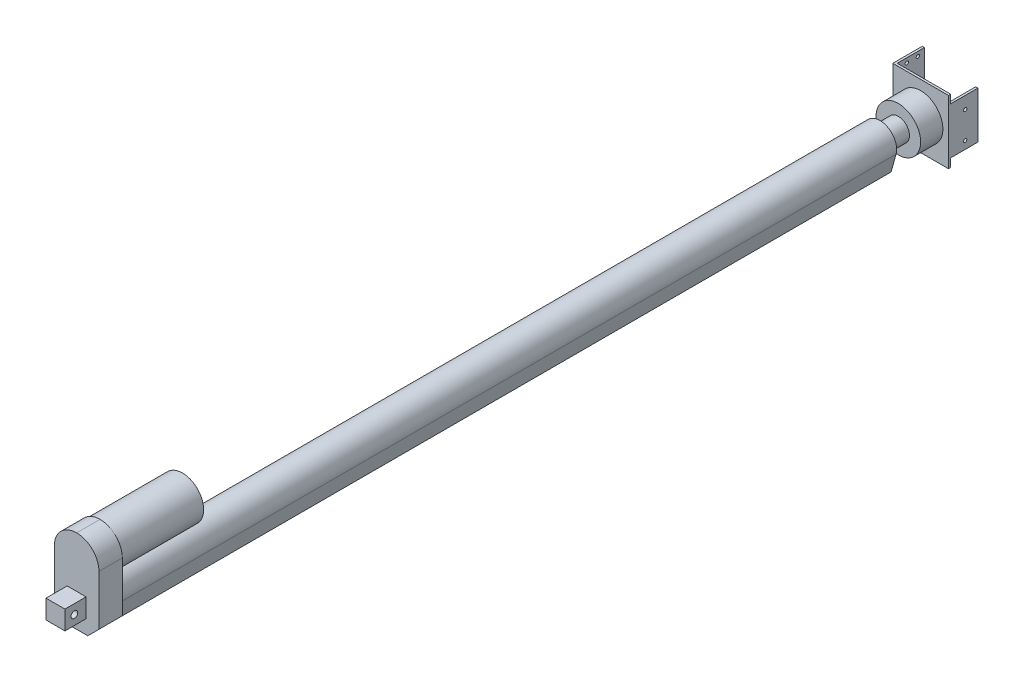
SolidWorks part; units mm, degrees
ref_plane "前视基准面" through (0, 0, 0) normal (0, 0, 1) x (1, 0, 0)
ref_plane "上视基准面" through (0, 0, 0) normal (0, 1, 0) x (1, 0, 0)
ref_plane "右视基准面" through (0, 0, 0) normal (1, 0, 0) x (0, 0, -1)
other "Configuration Table"
sketch "草图1" plane through (0, 0, 0) normal (0, 0, 1) x (1, 0, 0)
  line L1 (-20, 37.5) -> (20, 37.5)
  line L2 (-20, 37.5) -> (-20, -37.5)
  line L3 (-20, -37.5) -> (20, -37.5)
  line L4 (20, 37.5) -> (20, -37.5)
  dimension "D1" = 75
  dimension "D2" = 40
  dimension "D3" = 20
  dimension "D4" = 37.5
extrude "凸台-拉伸1" add sketch "草图1" along normal blind 21
fillet "圆角1" radius 20 2 edges at (-20, 37.5, 10.5) (20, 37.5, 10.5)
chamfer "倒角1" distance 10 angle 45 2 edges at (-20, -37.5, 10.5) (20, -37.5, 10.5)
sketch "草图2" plane through (0, 0, 0) normal (0, 0, -1) x (-1, 0, 0)
  line L0 (10, -37.5) -> (-10, -37.5) construction
  line L1 (-10, -37.5) -> (10, -37.5)
  line L2 (10, -37.5) -> (14.4499, -21.5251)
  line L3 (-10, -37.5) -> (-14.4499, -21.5251)
  arc A0 (14.4499, -21.5251) -> (-14.4499, -21.5251) centre (0, -17.5) ccw
  circle A1 centre (0, -17.5) radius 20 construction
  dimension "D1" = 30
  dimension "D2" = 40
extrude "凸台-拉伸2" add sketch "草图2" along normal blind 700
sketch "草图3" plane through (0, 0, 0) normal (0, 0, -1) x (-1, 0, 0)
  circle A0 centre (0, 17.5) radius 19
  arc A1 (20, 17.5) -> (0, 37.5) centre (0, 17.5) ccw construction
  dimension "D1" = 38
extrude "凸台-拉伸4" add sketch "草图3" along normal blind 74
sketch "草图4" plane through (0, 0, 21) normal (0, 0, 1) x (1, 0, 0)
  line L0 (-10, -37.5) -> (10, -37.5) construction
  line L1 (-8.5, -8) -> (8.5, -8)
  line L2 (-8.5, -8) -> (-8.5, -25)
  line L3 (-8.5, -25) -> (8.5, -25)
  line L4 (8.5, -8) -> (8.5, -25)
  dimension "D1" = 17
  dimension "D2" = 8.5
  dimension "D3" = 12.5
extrude "凸台-拉伸5" add sketch "草图4" along normal blind 19
sketch "草图5" plane through (-8.5, 0, 0) normal (-1, 0, 0) x (0, 0, 1)
  line L0 (40, -8) -> (40, -25) construction
  line L1 (40, -8) -> (21, -8) construction
  circle A0 centre (31.5, -16.5) radius 3
  dimension "D1" = 8.5
  dimension "D2" = 6
  dimension "D3" = 8.5
extrude "切除-拉伸1" cut sketch "草图5" against normal blind 19
sketch "草图6" plane through (0, 0, -700) normal (0, 0, -1) x (-1, 0, 0)
  circle A0 centre (0, -17.5) radius 10
  dimension "D1" = 20
extrude "凸台-拉伸6" add sketch "草图6" along normal blind 16.5
sketch "草图7" plane through (0, 0, -716.5) normal (0, 0, -1) x (-1, 0, 0)
  circle A0 centre (0, -17.5) radius 20
  dimension "D1" = 40
extrude "凸台-拉伸7" add sketch "草图7" along normal blind 20
sketch "草图8" plane through (0, 0, -736.5) normal (0, 0, -1) x (-1, 0, 0)
  line L1 (-25, 11.25) -> (25, 11.25)
  line L2 (-25, 11.25) -> (-25, -45.75)
  line L3 (-25, -45.75) -> (25, -45.75)
  line L4 (25, 11.25) -> (25, -45.75)
  circle A0 centre (0, -17.5) radius 20 construction
  dimension "D4" = 28.75
  dimension "D1" = 57
  dimension "D2" = 50
  dimension "D3" = 25
extrude "凸台-拉伸8" add sketch "草图8" along normal blind 2
sketch "草图9" plane through (0, 0, -738.5) normal (0, 0, -1) x (-1, 0, 0)
  line L0 (-25, -45.75) -> (25, -45.75) construction
  line L1 (25, 11.25) -> (23, 11.25)
  line L2 (25, 11.25) -> (25, -45.75)
  line L3 (25, -45.75) -> (23, -45.75)
  line L4 (23, 11.25) -> (23, -45.75)
  dimension "D1" = 2
extrude "凸台-拉伸9" add sketch "草图9" along normal blind 24.5
sketch "草图10" plane through (0, 0, -738.5) normal (0, 0, -1) x (-1, 0, 0)
  line L0 (-25, 11.25) -> (-25, -45.75) construction
  line L1 (-25, 3.75) -> (-23, 3.75)
  line L2 (-25, 3.75) -> (-25, -38.25)
  line L3 (-25, -38.25) -> (-23, -38.25)
  line L4 (-23, 3.75) -> (-23, -38.25)
  line L5 (23, 11.25) -> (-25, 11.25) construction
  dimension "D1" = 42
  dimension "D2" = 7.5
  dimension "D3" = 2
extrude "凸台-拉伸10" add sketch "草图10" along normal blind 24.5
sketch "草图11" plane through (-25, 0, 0) normal (-1, 0, 0) x (0, 0, 1)
  line L0 (-763, -45.75) -> (-763, 11.25) construction
  line L1 (-757, 7.25) -> (-747.1, 7.25) construction
  line L2 (-757, 7.25) -> (-757, -41.75) construction
  line L3 (-757, -41.75) -> (-747.1, -41.75) construction
  line L4 (-747.1, 7.25) -> (-747.1, -41.75) construction
  line L5 (-763, 11.25) -> (-736.5, 11.25) construction
  circle A0 centre (-757, 7.25) radius 1.5
  circle A1 centre (-747.1, 7.25) radius 1.5
  circle A2 centre (-747.1, -41.75) radius 1.5
  circle A3 centre (-757, -41.75) radius 1.5
  dimension "D5" = 3
  dimension "D1" = 9.9
  dimension "D2" = 49
  dimension "D3" = 6
  dimension "D4" = 4
extrude "切除-拉伸2" cut sketch "草图11" against normal blind 10
sketch "草图12" plane through (-25, 0, 0) normal (-1, 0, 0) x (0, 0, 1)
  circle A1 centre (-752.05, -31.25) radius 1.5
  circle A2 centre (-747.1, -41.75) radius 1.5 construction
  circle A3 centre (-757, -41.75) radius 1.5 construction
  dimension "D1" = 10.5
  dimension "D2" = 4.95
  dimension "D3" = 3
extrude "切除-拉伸3" cut sketch "草图12" against normal blind 10
sketch "草图13" plane through (25, 0, 0) normal (1, 0, 0) x (0, 0, -1)
  line L0 (763, 3.75) -> (738.5, 3.75) construction
  line L2 (763, 3.75) -> (763, -38.25) construction
  circle A0 centre (751.5, -7.25) radius 1.5
  circle A1 centre (751.5, -31.25) radius 1.5
  point P6 (0, 0)
  dimension "D1" = 24
  dimension "D4" = 3
  dimension "D5" = 3
  dimension "D2" = 11
  dimension "D3" = 11.5
extrude "切除-拉伸4" cut sketch "草图13" against normal blind 10
